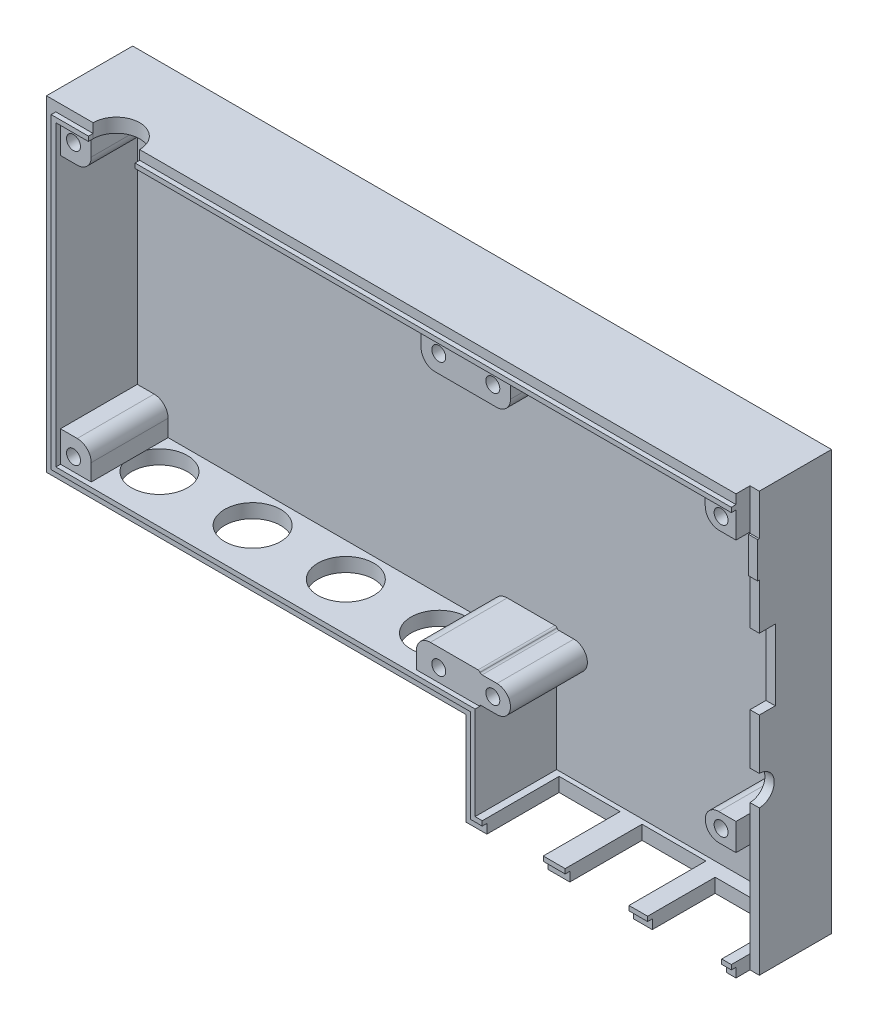
SolidWorks part; units mm, degrees
ref_plane "Front Plane" through (0, 0, 0) normal (0, 0, 1) x (1, 0, 0)
ref_plane "Top Plane" through (0, 0, 0) normal (0, 1, 0) x (1, 0, 0)
ref_plane "Right Plane" through (0, 0, 0) normal (1, 0, 0) x (0, 0, -1)
sketch "Sketch1" plane through (0, 0, 0) normal (0, 0, 1) x (1, 0, 0)
  line L1 (30, -45) -> (-30, -45)
  line L2 (30, -45) -> (30, 45)
  line L3 (30, 45) -> (-30, 45)
  line L4 (-30, -45) -> (-30, 45)
  line L5 (30, -45) -> (-30, 45) construction
  line L6 (30, 45) -> (-30, -45) construction
  circle A0 centre (-24.2, -18.8) radius 1.5
  circle A1 centre (-24.2, 39.2) radius 1.5
  circle A2 centre (24.8, 39.2) radius 1.5
  circle A4 centre (24.8, -18.8) radius 1.5
  point P0 (0, 0)
  dimension "D4" = 5.8
  dimension "D5" = 3
  dimension "D6" = 58
  dimension "D1" = 60
  dimension "D2" = 90
  dimension "D3" = 5.8
  dimension "D7" = 49
extrude "Boss-Extrude1" add sketch "Sketch1" along normal mid plane 2
sketch "Sketch2" plane through (0, 0, 1) normal (0, 0, 1) x (1, 0, 0)
  line L0 (28, 42) -> (-27, 42)
  line L1 (-27, 42) -> (-27, -42)
  line L4 (-30, 45) -> (-30, -45)
  line L5 (-30, -45) -> (30, -45)
  line L6 (30, -45) -> (30, 45)
  line L7 (30, 45) -> (-30, 45)
  line L8 (-30, 45) -> (-30, -45)
  line L9 (-30, -45) -> (30, -45)
  line L10 (30, -45) -> (30, 45)
  line L11 (30, 45) -> (-30, 45)
  line L12 (28, 42) -> (28, 45)
  line L14 (-27, -42) -> (28, -42)
  line L18 (-30, -45) -> (28, -45)
  line L19 (28, -42) -> (28, -45)
  line M5 (-30, 45) -> (-30, -45)
  line M6 (-30, -45) -> (30, -45)
  dimension "D3" = 2
  dimension "D4" = 3
  dimension "D2" = 3
  dimension "D5" = 3
  dimension "D1" = 0
extrude "Boss-Extrude2" add sketch "Sketch2" along normal blind 16.5 contours L1 L0 L12 L11 M5 M6 region at (0.5, 43.0707, 1)
sketch "Sketch3" plane through (0, 0, 1) normal (0, 0, 1) x (1, 0, 0)
  line L0 (28, -45) -> (30, -45) construction
  line L1 (28, 45) -> (30, 45)
  line L2 (28, 45) -> (28, -45)
  line L3 (28, -45) -> (30, -45)
  line L4 (30, 45) -> (30, -45)
  line L5 (30, -45) -> (30, 45) construction
extrude "Boss-Extrude3" add sketch "Sketch3" along normal blind 13.5
sketch "Sketch4" plane through (0, 0, 17.5) normal (0, 0, 1) x (1, 0, 0)
  line L0 (28, -43) -> (-28, -43)
  line L1 (-28, -43) -> (-28, 43)
  line L2 (-28, 43) -> (28, 43)
  line L3 (28, -42) -> (28, -43)
  line L4 (28, 43) -> (28, 42)
  line L8 (28, -45) -> (28, -42)
  line L9 (28, -42) -> (-27, -42)
  line L10 (-27, -42) -> (-27, 42)
  line L11 (-27, 42) -> (28, 42)
  line L12 (28, 42) -> (28, 45)
  line L13 (28, 45) -> (-30, 45)
  line L14 (-30, 45) -> (-30, -45)
  line L15 (-30, -45) -> (28, -45)
  line L17 (28, -42) -> (-27, -42)
  line L18 (-27, -42) -> (-27, 42)
  line L19 (-27, 42) -> (28, 42)
  dimension "D1" = 0
  dimension "D2" = 1
extrude "Boss-Extrude4" add sketch "Sketch4" along normal blind 1
sketch "Sketch5" plane through (0, 0, 18.5) normal (0, 0, 1) x (1, 0, 0)
  line L0 (28, -42) -> (-27, -42) construction
  line L1 (-25.47, -42) -> (-12.37, -42)
  line L2 (-25.47, -42) -> (-25.47, -45)
  line L3 (-25.47, -45) -> (-12.37, -45)
  line L4 (-12.37, -42) -> (-12.37, -45)
  line L5 (-30, 45) -> (-30, -45) construction
  line L6 (-7.67, -42) -> (6.03, -42)
  line L7 (-7.67, -42) -> (-7.67, -45)
  line L8 (-7.67, -45) -> (6.03, -45)
  line L9 (6.03, -42) -> (6.03, -45)
  line L10 (-30, -45) -> (28, -45) construction
  dimension "D1" = 4.53
  dimension "D2" = 13.1
  dimension "D3" = 4.7
  dimension "D4" = 13.7
extrude "Cut-Extrude1" cut sketch "Sketch5" against normal blind 16.5
sketch "Sketch6" plane through (0, 0, 18.5) normal (0, 0, 1) x (1, 0, 0)
  line L0 (28, -42) -> (6.03, -42) construction
  line L1 (10.03, -42) -> (25.93, -42)
  line L2 (10.03, -42) -> (10.03, -45)
  line L3 (10.03, -45) -> (25.93, -45)
  line L4 (25.93, -42) -> (25.93, -45)
  line L5 (6.03, -45) -> (6.03, -43) construction
  line L8 (6.03, -45) -> (28, -45) construction
  dimension "D1" = 15.9
  dimension "D2" = 4
extrude "Cut-Extrude2" cut sketch "Sketch6" against normal blind 14.5
sketch "Sketch7" plane through (0, 0, 1) normal (0, 0, 1) x (1, 0, 0)
  line L0 (-27, -15.9) -> (-23.3, -15.9)
  line L1 (-27, -42) -> (-27, 42) construction
  line L2 (0.5, 42) -> (0.5, -42) construction
  line L3 (-23.3, -21.7) -> (-27, -21.7)
  line L4 (-20.4, 42) -> (-20.4, 35.4)
  line L5 (28, 42) -> (-27, 42) construction
  line L6 (-20.4, 35.4) -> (-27, 35.4)
  line L7 (24.3, -21.7) -> (28, -21.7)
  line L8 (28, -15.9) -> (24.3, -15.9)
  line L10 (21.4, 36.4) -> (28, 36.4)
  line L11 (21.4, 42) -> (21.4, 36.4)
  line L12 (-20.4, 42) -> (-27, 42)
  line L13 (-27, -42) -> (28, -42) construction
  line L14 (-27, 42) -> (-27, 35.4)
  line L15 (-27, -15.9) -> (-27, -21.7)
  line L16 (21.4, 42) -> (28, 42)
  line L17 (28, 42) -> (28, 36.4)
  line L18 (28, -15.9) -> (28, -21.7)
  circle A0 centre (-24.2, -18.8) radius 1.5 construction
  arc A1 (-23.3, -15.9) -> (-23.3, -21.7) centre (-23.3, -18.8) cw
  arc A2 (24.3, -15.9) -> (24.3, -21.7) centre (24.3, -18.8) ccw
  circle A3 centre (24.8, -18.8) radius 1.5 construction
  circle A4 centre (24.8, 39.2) radius 1.5 construction
  circle A5 centre (-24.2, 39.2) radius 1.5 construction
  circle A6 centre (24.8, -18.8) radius 1.5
  circle A7 centre (-24.2, -18.8) radius 1.5
  circle A8 centre (24.8, 39.2) radius 1.5
  circle A9 centre (-24.2, 39.2) radius 1.5
  dimension "D6" = 5.6
  dimension "D1" = 6.6
  dimension "D2" = 6.6
  dimension "D3" = 5.8
  dimension "D4" = 3.7
  dimension "D5" = 2.9
extrude "Boss-Extrude5" add sketch "Sketch7" along normal blind 16.5
fillet "Fillet3" radius 3 2 edges at (21.4, 36.4, 9.25) (-20.4, 35.4, 9.25)
sketch "Sketch9" plane through (30, 0, 0) normal (1, 0, 0) x (0, 0, -1)
  line L0 (-14.5, -45) -> (-14.5, 45) construction
  line L2 (-17.5, -45) -> (-14.5, -45) construction
  arc A0 (-14.5, -13.88) -> (-14.5, -7.48) centre (-14.5, -10.68) ccw
  point P7 (-16, -45)
  dimension "D3" = 3.2
  dimension "D1" = 31.12
  dimension "D2" = 6.4
extrude "Cut-Extrude3" cut sketch "Sketch9" against normal blind 2 and the other way through all
sketch "Sketch10" plane through (0, 0, 14.5) normal (0, 0, 1) x (1, 0, 0)
  line L0 (28, 36.4) -> (28, -7.48) construction
  line L1 (28, 3.38) -> (30, 3.38)
  line L2 (28, 3.38) -> (28, 18.58)
  line L3 (28, 18.58) -> (30, 18.58)
  line L4 (30, 3.38) -> (30, 18.58)
  line L7 (30, -7.48) -> (28, -7.48) construction
  line L8 (30, -7.48) -> (30, 45) construction
  point P8 (29, -7.48)
  dimension "D1" = 15.2
  dimension "D2" = 10.86
extrude "Cut-Extrude4" cut sketch "Sketch10" against normal blind 3.43
sketch "Sketch11" plane through (0, 0, 14.5) normal (0, 0, 1) x (1, 0, 0)
  line L0 (28, 36.4) -> (28, 18.58) construction
  line L1 (28, 28.47) -> (30, 28.47)
  line L2 (28, 28.47) -> (28, 36.17)
  line L3 (28, 36.17) -> (30, 36.17)
  line L4 (30, 28.47) -> (30, 36.17)
  line L5 (30, 18.58) -> (30, 45) construction
  line L6 (30, 18.58) -> (28, 18.58) construction
  dimension "D1" = 9.89
  dimension "D2" = 7.7
extrude "Boss-Extrude6" add sketch "Sketch11" along normal blind 0.35
sketch "Sketch12" plane through (0, 0, 1) normal (0, 0, 1) x (1, 0, 0)
  line L0 (-27, 35.4) -> (-23.4, 35.4) construction
  line L1 (-23.2, 35.4) -> (-21.7, 35.4)
  line L2 (-25.2, 33.4) -> (-25.2, -13.9)
  line L3 (-23.2, -15.9) -> (-21.7, -15.9)
  line L4 (-19.7, 33.4) -> (-19.7, -13.9)
  line L5 (-23.3, -15.9) -> (-27, -15.9) construction
  line L6 (28, 45) -> (-30, 45) construction
  line L7 (-9.11, 40.7) -> (9.11, 40.7)
  line L8 (-9.11, 40.7) -> (-9.11, 37.7)
  line L9 (-9.11, 37.7) -> (9.11, 37.7)
  line L10 (9.11, 40.7) -> (9.11, 37.7)
  line L11 (30, 36.17) -> (30, 45) construction
  line L12 (-30, 45) -> (-30, -45) construction
  line L13 (30, -7.48) -> (30, 3.38) construction
  line L14 (7.59, -0.85) -> (25.77, -0.85)
  line L15 (7.59, -0.85) -> (7.59, -3.8529)
  line L16 (7.59, -3.8529) -> (25.77, -3.8529)
  line L17 (25.77, -0.85) -> (25.77, -3.8529)
  arc A0 (-21.7, -15.9) -> (-19.7, -13.9) centre (-21.7, -13.9) ccw
  arc A1 (-25.2, -13.9) -> (-23.2, -15.9) centre (-23.2, -13.9) ccw
  arc A2 (-21.7, 35.4) -> (-19.7, 33.4) centre (-21.7, 33.4) cw
  arc A3 (-23.2, 35.4) -> (-25.2, 33.4) centre (-23.2, 33.4) ccw
  point P16 (-25.2, 35.4)
  dimension "D2" = 2
  dimension "D1" = 5.5
  dimension "D3" = 4.3
  dimension "D4" = 20.89
  dimension "D5" = 20.89
  dimension "D6" = 3
  dimension "D7" = 45.85
  dimension "D8" = 4.23
  dimension "D9" = 18.18
  dimension "D10" = 3.0029
extrude "Cut-Extrude5" [suppressed] cut sketch "Sketch12" against normal up to next
sketch "Sketch13" plane through (0, 0, -1) normal (0, 0, -1) x (-1, 0, 0)
  line L1 (30, 45) -> (120, 45)
  line L2 (30, 45) -> (30, -25)
  line L3 (30, -25) -> (120, -25)
  line L4 (120, 45) -> (120, -25)
  dimension "D1" = 70
  dimension "D2" = 90
extrude "Boss-Extrude7" add sketch "Sketch13" against normal up to surface (2 mm away) up to face at (0.5, 3.8754, 1)
sketch "Sketch14" plane through (0, 0, 1) normal (0, 0, 1) x (1, 0, 0)
  line L0 (-33, 42) -> (-117, 42)
  line L1 (-117, 42) -> (-117, -22)
  line L2 (-117, -22) -> (-33, -22)
  line L3 (-33, -22) -> (-33, 42)
  line L4 (-30, -25) -> (-30, 45)
  line L5 (-30, 45) -> (-120, 45)
  line L6 (-120, 45) -> (-120, -25)
  line L7 (-120, -25) -> (-30, -25)
  line L8 (-30, -25) -> (-30, 45)
  line L9 (-30, 45) -> (-120, 45)
  line L10 (-120, 45) -> (-120, -25)
  line L11 (-120, -25) -> (-30, -25)
  dimension "D1" = 0
  dimension "D2" = 3
extrude "Boss-Extrude8" add sketch "Sketch14" along normal up to surface (16.5 mm away) up to face at (-13.8675, 0, 17.5)
sketch "Sketch15" plane through (0, 0, 17.5) normal (0, 0, 1) x (1, 0, 0)
  line L10 (-25.47, -45) -> (-25.47, -43)
  line L11 (-25.47, -43) -> (-28, -43)
  line L12 (-28, -43) -> (-28, 43)
  line L13 (-28, 43) -> (28, 43)
  line L14 (28, 43) -> (28, 45)
  line L15 (28, 45) -> (-120, 45)
  line L16 (-120, 45) -> (-120, -25)
  line L17 (-120, -25) -> (-30, -25)
  line L18 (-30, -25) -> (-30, -45)
  line L19 (-30, -45) -> (-25.47, -45)
  line L20 (-25.47, -45) -> (-25.47, -43)
  line L21 (-25.47, -43) -> (-28, -43)
  line L22 (-28, -43) -> (-28, 43)
  line L23 (-28, 43) -> (28, 43)
  line L24 (28, 43) -> (28, 45)
  line L25 (28, 45) -> (-120, 45)
  line L26 (-120, 45) -> (-120, -25)
  line L27 (-120, -25) -> (-30, -25)
  line L28 (-30, -25) -> (-30, -45)
  line L29 (-30, -45) -> (-25.47, -45)
  line L30 (-27, 42) -> (28, 42) construction
  line L31 (-117, 42) -> (-33, 42)
  line L32 (-117, 42) -> (-117, -22)
  line L33 (-117, -22) -> (-33, -22)
  line L34 (-118, 43) -> (-118, -23)
  line L35 (-118, -23) -> (-32, -23)
  line L36 (-32, -23) -> (-32, 43)
  line L37 (-32, 43) -> (-118, 43)
  line L38 (-118, 43) -> (-118, -23)
  line L39 (-118, -23) -> (-32, -23)
  line L40 (-32, -23) -> (-32, 43)
  line L41 (-32, 43) -> (-118, 43)
  line L42 (-33, 42) -> (-33, -22)
  line L43 (-32, 43) -> (-28, 43)
  line L44 (-32, 43) -> (-32, 42)
  line L45 (-32, 42) -> (-28, 42)
  line L46 (-28, 43) -> (-28, 42)
  line L47 (-28, 43) -> (-28, -43) construction
  line L48 (-32, -23) -> (-28, -23)
  line L49 (-32, -23) -> (-32, -22)
  line L50 (-32, -22) -> (-28, -22)
  line L51 (-28, -23) -> (-28, -22)
  line M25 (-33, 42) -> (-33, -22)
  line M26 (-33, -22) -> (-117, -22)
  line M27 (-117, -22) -> (-117, 42)
  line M28 (-117, 42) -> (-33, 42)
  dimension "D1" = 0
  dimension "D2" = 1
extrude "Boss-Extrude9" add sketch "Sketch15" along normal blind 1 contours L40 L41 L38 L39 M28 M25 M26 M27 | L50 L40 L48 L22 | L43 L46 L45 L44 region at (-30, -22.5, 17.5) region at (-75, -22.8916, 17.5)
sketch "Sketch16" plane through (0, 0, 18.5) normal (0, 0, 1) x (1, 0, 0)
  line L1 (-33, 42) -> (-27, 42)
  line L2 (-33, 42) -> (-33, -22)
  line L3 (-33, -22) -> (-27, -22)
  line L4 (-27, 42) -> (-27, -22)
  line L6 (-33, 42) -> (-33, -22) construction
  line L7 (-27, -42) -> (-27, 42) construction
  line L8 (-32, -22) -> (-28, -22) construction
  line L10 (-32, 42) -> (-28, 42) construction
extrude "Cut-Extrude6" cut sketch "Sketch16" against normal blind 1
sketch "Sketch17" plane through (0, -25, 0) normal (0, -1, 0) x (1, 0, 0)
  line L0 (-30, 8.25) -> (-120, 8.25) construction
  line L1 (-30, 17.5) -> (-30, -1) construction
  line L2 (-120, 17.5) -> (-120, -1) construction
  circle A0 centre (-45, 8.25) radius 6
  circle A1 centre (-65, 8.25) radius 6
  circle A2 centre (-85, 8.25) radius 6
  circle A3 centre (-105, 8.25) radius 6
  dimension "D1" = 12
  dimension "D2" = 15
  dimension "D3" = 20
  dimension "D4" = 20
  dimension "D5" = 20
extrude "Cut-Extrude7" cut sketch "Sketch17" against normal up to next and the other way through all
sketch "Sketch19" plane through (0, 0, 1) normal (0, 0, 1) x (1, 0, 0)
  line L0 (-117, -15.4) -> (-113.4, -15.4)
  line L1 (-117, 42) -> (-117, -22) construction
  line L2 (-110.4, -18.4) -> (-110.4, -22)
  line L3 (-117, -22) -> (-33, -22) construction
  line L4 (-40.6, -22) -> (-40.6, -18.4)
  line L5 (-37.6, -15.4) -> (-33, -15.4)
  line L6 (-33, 42) -> (-33, -22) construction
  line L7 (-39.6, 42) -> (-39.6, 38.4)
  line L8 (-117, 42) -> (28, 42) construction
  line L9 (-36.6, 35.4) -> (-33, 35.4)
  line L10 (-33, -22) -> (-33, 42) construction
  line L11 (-110.4, 42) -> (-110.4, 38.4)
  line L12 (-33, 42) -> (-117, 42) construction
  line L13 (-113.4, 35.4) -> (-117, 35.4)
  line L14 (-117, -22) -> (-117, 42) construction
  line L15 (-110.4, 42) -> (-117, 42)
  line L16 (-117, 42) -> (-117, 35.4)
  line L17 (-117, -15.4) -> (-117, -22)
  line L18 (-117, -22) -> (-110.4, -22)
  line L19 (-40.6, -22) -> (-33, -22)
  line L20 (-33, -22) -> (-33, -15.4)
  line L21 (-39.6, 42) -> (-33, 42)
  line L22 (-33, 42) -> (-33, 35.4)
  arc A0 (-40.6, -18.4) -> (-37.6, -15.4) centre (-37.6, -18.4) cw
  arc A1 (-113.4, -15.4) -> (-110.4, -18.4) centre (-113.4, -18.4) cw
  arc A2 (-39.6, 38.4) -> (-36.6, 35.4) centre (-36.6, 38.4) ccw
  arc A3 (-110.4, 38.4) -> (-113.4, 35.4) centre (-113.4, 38.4) cw
  point P32 (-40.6, -15.4)
  point P35 (-110.4, -15.4)
  point P40 (-110.4, 35.4)
  dimension "D7" = 3
  dimension "D1" = 6.6
  dimension "D2" = 6.6
  dimension "D3" = 6.6
  dimension "D4" = 6.6
  dimension "D5" = 7.6
  dimension "D6" = 6.6
  dimension "D8" = 6.6
extrude "Boss-Extrude10" add sketch "Sketch19" along normal up to surface (16.5 mm away) up to face at (-48.9117, -8, 17.5)
sketch "Sketch18" plane through (0, 0, 1) normal (0, 0, 1) x (1, 0, 0)
  line L0 (-33, -15.4) -> (-33, 35.4) construction
  line L1 (-110.4, -22) -> (-40.6, -22) construction
  line L2 (-117, 35.4) -> (-117, -15.4) construction
  line L3 (-39.6, 42) -> (-110.4, 42) construction
  circle A0 centre (-114.2, 39.2) radius 1.5
  circle A1 centre (-35.8, 39.2) radius 1.5
  circle A2 centre (-35.8, -19.2) radius 1.5
  circle A3 centre (-114.2, -19.2) radius 1.5
  dimension "D1" = 3
  dimension "D2" = 2.8
  dimension "D3" = 2.8
  dimension "D4" = 2.8
  dimension "D5" = 2.8
extrude "Cut-Extrude8" cut sketch "Sketch18" along normal blind 56 and the other way blind 19
sketch "Sketch20" plane through (0, 0, 17.5) normal (0, 0, 1) x (1, 0, 0)
  line L0 (-27, -15.9) -> (-27, 35.4) construction
  line L1 (-33, 35.4) -> (-27, 35.4)
  line L2 (-33, 35.4) -> (-33, -15.4)
  line L3 (-33, -15.4) -> (-27, -15.4)
  line L4 (-27, 35.4) -> (-27, -15.4)
  line L5 (-33, -15.4) -> (-37.6, -15.4) construction
extrude "Cut-Extrude9" cut sketch "Sketch20" against normal up to surface (16.5 mm away) up to face at (-75.1875, 10, 1)
fillet "Fillet4" radius 0.5 1 edges at (-27, -15.9, 9.25)
fillet "Fillet5" radius 0.5 1 edges at (-27, -15.4, 9.25)
sketch "Sketch21" plane through (0, 45, 0) normal (0, 1, 0) x (1, 0, 0)
  line L1 (28, -17.5) -> (-120, -17.5) construction
  line L2 (-110, -17.5) -> (-110, -18.5)
  line L3 (28, -18.5) -> (-118, -18.5) construction
  line L4 (-110, -18.5) -> (-100, -18.5)
  line L5 (-100, -18.5) -> (-100, -17.5)
  arc A0 (-110, -17.5) -> (-100, -17.5) centre (-105, -17.5) cw
  dimension "D1" = 5
  dimension "D2" = 10
  dimension "D3" = 10
extrude "Cut-Extrude10" cut sketch "Sketch21" against normal blind 4
